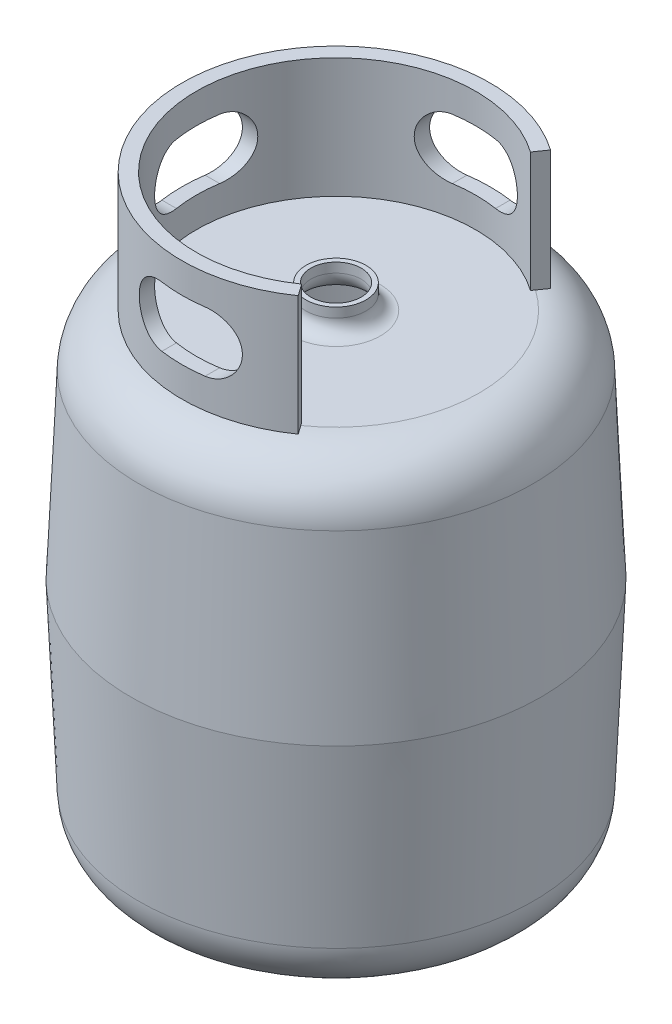
SolidWorks part; units mm, degrees
material "1060 Alloy"
ref_plane "Front Plane" through (0, 0, 0) normal (0, 0, 1) x (1, 0, 0)
ref_plane "Top Plane" through (0, 0, 0) normal (0, 1, 0) x (1, 0, 0)
ref_plane "Right Plane" through (0, 0, 0) normal (1, 0, 0) x (0, 0, -1)
sketch "Sketch1" plane through (0, 0, 0) normal (0, 0, 1) x (1, 0, 0)
  line L0 (0, -179.2118) -> (0, 179.2118) construction
  line L1 (-193.9008, 0) -> (193.9008, 0) construction
  line L2 (0, 213.75) -> (-25, 213.75)
  line L3 (-25, 213.75) -> (-25, 205.75)
  line L4 (-37, 193.75) -> (-119.4219, 193.75)
  line L5 (-164.379, 150.7129) -> (-170.9593, 0)
  line L6 (-170.9593, 0) -> (-164.379, -150.7129)
  line L7 (-119.4219, -193.75) -> (0, -193.75)
  line L8 (0, 213.75) -> (0, -193.75)
  arc A0 (-164.379, 150.7129) -> (-119.4219, 193.75) centre (-119.4219, 148.75) cw
  arc A1 (-119.4219, -193.75) -> (-164.379, -150.7129) centre (-119.4219, -148.75) cw
  arc A2 (-37, 193.75) -> (-25, 205.75) centre (-37, 205.75) ccw
  point P4 (0, 0)
  point P8 (0, 0)
  point P17 (-162.5, 193.75)
  point P20 (-162.5, -193.75)
  point P23 (-25, 193.75)
  dimension "D8" = 45
  dimension "D9" = 12
  dimension "D1" = 25
  dimension "D2" = 162.5
  dimension "D3" = 162.5
  dimension "D4" = 193.75
  dimension "D5" = 193.75
  dimension "D6" = 20
  dimension "D7" = 92.5
revolve "Revolve1" add sketch "Sketch1" angle 360 about L8
shell "Shell1" thickness 4 removed face at (-25, 213.75, 0)
sketch "Sketch2" plane through (0, 193.75, 0) normal (0, 1, 0) x (1, 0, 0)
  line L0 (0, -194.2129) -> (0, 194.2129) construction
  line L1 (-245.2833, 0) -> (245.2833, 0) construction
  line L2 (0, 0) -> (73.6598, 105.197)
  line L3 (0, 0) -> (73.6598, -105.197)
  arc A0 (73.6598, 105.197) -> (73.6598, -105.197) centre (0, 0) ccw
  arc A1 (66.7768, 95.3672) -> (66.7768, -95.3672) centre (0, 0) ccw
  circle A2 centre (0, 0) radius 119.4219 construction
  point P9 (0, 0)
  point P12 (0, 0)
  circle M4 centre (0, 0) radius 119.4219
  dimension "D1" = 3
  dimension "D2" = 12
  dimension "D3" = 55
extrude "Boss-Extrude1" add sketch "Sketch2" along normal blind 100 contours L2 A0 L3 M4 | A1 L2 L3 M4 region at (-116.7258, 193.75, 0) region at (-122.69, 193.75, 0)
sketch "Sketch3" plane through (0, 0, 0) normal (0, 0, 1) x (1, 0, 0)
  line L0 (0, -321.6688) -> (0, 321.6688) construction
  line L1 (-18, 268.75) -> (18, 268.75)
  line L2 (-18, 218.75) -> (18, 218.75)
  line L5 (73.6598, 293.75) -> (-128.4219, 293.75) construction
  arc A0 (18, 218.75) -> (18, 268.75) centre (18, 243.75) ccw
  arc A1 (-18, 218.75) -> (-18, 268.75) centre (-18, 243.75) cw
  point P4 (0, 0)
  point P6 (43, 243.75)
  point P8 (-43, 243.75)
  dimension "D1" = 50
  dimension "D3" = 50
  dimension "D2" = 86
extrude "Cut-Extrude1" cut sketch "Sketch3" against normal blind 251 and the other way blind 203
sketch "Sketch5" plane through (0, 0, 0) normal (1, 0, 0) x (0, 0, -1)
  line L0 (-18, 243.75) -> (18, 243.75) construction
  line L1 (-18, 268.75) -> (18, 268.75)
  line L2 (-18, 218.75) -> (18, 218.75)
  line L3 (0, 293.75) -> (0, 193.75) construction
  line L4 (116.4219, 293.75) -> (-116.4219, 293.75) construction
  arc A0 (-18, 268.75) -> (-18, 218.75) centre (-18, 243.75) ccw
  arc A1 (18, 218.75) -> (18, 268.75) centre (18, 243.75) ccw
  point P2 (0, 243.75)
  point P7 (-43, 243.75)
  point P8 (43, 243.75)
  dimension "D2" = 50
  dimension "D1" = 86
  dimension "D3" = 50
extrude "Cut-Extrude2" cut sketch "Sketch5" against normal blind 251
